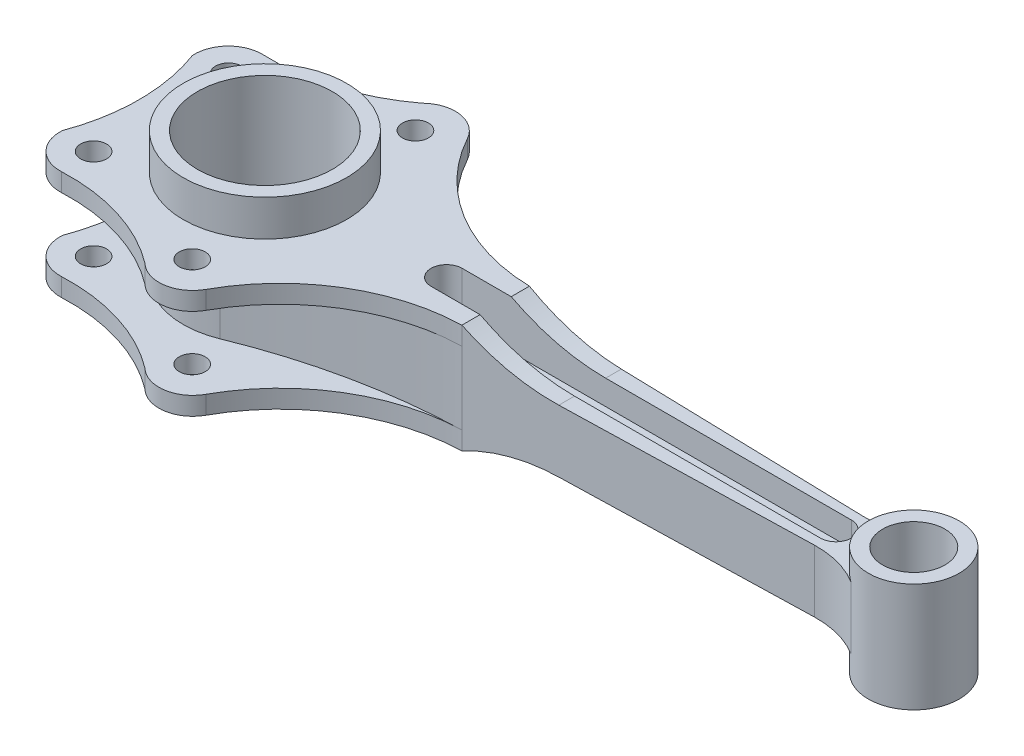
SolidWorks part; units mm, degrees
ref_plane "Front Plane" through (0, 0, 0) normal (0, 0, 1) x (1, 0, 0)
ref_plane "Top Plane" through (0, 0, 0) normal (0, 1, 0) x (1, 0, 0)
ref_plane "Right Plane" through (0, 0, 0) normal (1, 0, 0) x (0, 0, -1)
sketch "Sketch1" plane through (0, 0, 0) normal (0, 1, 0) x (1, 0, 0)
  line L0 (0, 96.3431) -> (0, -94.8456) construction
  line L1 (-187.9024, 0) -> (250, 0) construction
  line L2 (88.9041, 13.0022) -> (221.1878, 9.4949)
  line L3 (88.9041, -13.0022) -> (221.1878, -9.4949)
  line L4 (70, 0) -> (220, 0) construction
  line L5 (70, 6) -> (220, 6)
  line L6 (70, -6) -> (220, -6)
  circle A0 centre (0, 0) radius 31.5
  circle A1 centre (0, 0) radius 26
  circle A2 centre (250, 0) radius 17.5
  circle A3 centre (250, 0) radius 12
  circle A4 centre (15, 43) radius 5
  circle A5 centre (-40, 26) radius 5
  arc A6 (7.1798, 53.3914) -> (27.6805, 50.3597) centre (16.2817, 44.1094) cw
  arc A7 (-52.983, 25.0335) -> (-39.4311, 38.9301) centre (-40.0149, 25.9432) cw
  arc A8 (-39.4311, 38.9301) -> (7.1798, 53.3914) centre (-36.1982, 110.8575) ccw
  arc A9 (27.6805, 50.3597) -> (88.9041, 13.0022) centre (90.8125, 84.977) ccw
  circle A10 centre (-40, -26) radius 5
  circle A11 centre (15, -43) radius 5
  arc A12 (27.6805, -50.3597) -> (88.9041, -13.0022) centre (90.8125, -84.977) cw
  arc A13 (7.1798, -53.3914) -> (27.6805, -50.3597) centre (16.2817, -44.1094) ccw
  arc A14 (-52.983, -25.0335) -> (-39.4311, -38.9301) centre (-40.0149, -25.9432) ccw
  arc A15 (-39.4311, -38.9301) -> (7.1798, -53.3914) centre (-36.1982, -110.8575) cw
  arc A16 (-52.983, 25.0335) -> (-52.983, -25.0335) centre (-120.491, 0) cw
  arc A17 (240.7051, 14.8275) -> (221.1878, 9.4949) centre (222.1154, 44.4826) cw
  arc A18 (240.7051, -14.8275) -> (221.1878, -9.4949) centre (222.1154, -44.4826) ccw
  arc A19 (70, 6) -> (70, -6) centre (70, 0) ccw
  arc A20 (220, -6) -> (220, 6) centre (220, 0) ccw
  point P43 (145, 0)
  dimension "D1" = 63
  dimension "D2" = 52
  dimension "D4" = 24
  dimension "D5" = 35
  dimension "D6" = 10
  dimension "D7" = 10
  dimension "D12" = 13
  dimension "D13" = 13
  dimension "D14" = 72
  dimension "D15" = 72
  dimension "D16" = 72
  dimension "D17" = 35
  dimension "D18" = 35
  dimension "D19" = 6
  dimension "D3" = 250
  dimension "D8" = 15
  dimension "D9" = 26
  dimension "D10" = 17
  dimension "D11" = 40
  dimension "D20" = 150
  dimension "D21" = 30
  dimension "D23" = 3.4949
extrude "Boss-Extrude1" add sketch "Sketch1" along normal mid plane 42 contours A18 A2 A17 L2 A9 A6 A8 A7 A13 A12 L3 A20 L6 A19 L5 A10 A5 A4 A0 A11 | L6 A20 L5 A19 region at (41.4087, 0, 0)
sketch "Sketch2" plane through (0, 0, 0) normal (0, 0, 1) x (1, 0, 0)
  line L0 (240.7051, 21) -> (221.1878, 21) construction
  line L1 (88.9041, 21) -> (221.1878, 21) construction
  line L3 (240.7051, 21) -> (221.1878, 21)
  line L4 (88.9041, 21) -> (221.1878, 21)
  line L6 (0, 0) -> (269.5596, 0) construction
  line L7 (240.7051, 12) -> (125.2772, 12)
  line L9 (240.7051, 21) -> (240.7051, -21) construction
  line L10 (240.7051, -12) -> (125.2772, -12)
  line L11 (240.7051, -21) -> (221.1878, -21)
  line L12 (88.9041, -21) -> (221.1878, -21)
  line L13 (240.7051, 21) -> (240.7051, 12)
  line L14 (240.7051, -12) -> (240.7051, -21)
  arc A0 (88.9041, 21) -> (125.2772, 12) centre (125.2772, 90) ccw
  arc A1 (88.9041, -21) -> (125.2772, -12) centre (125.2772, -90) cw
  point P12 (0, 0)
  dimension "D2" = 78
  dimension "D1" = 9
extrude "Cut-Extrude1" cut sketch "Sketch2" against normal through all both and the other way through all
extrude "Boss-Extrude2" add sketch "Sketch1<3>" along normal mid plane 42 contours A2 A3 region at (258.2335, 0, -14.8788)
sketch "Sketch1<3>" plane through (0, 0, 0) normal (0, 1, 0) x (1, 0, 0) same geometry as "Sketch1"
extrude "Boss-Extrude3" add sketch "Sketch1<4>" along normal mid plane 70 contours A0 | A1
sketch "Sketch1<4>" plane through (0, 0, 0) normal (0, 1, 0) x (1, 0, 0) same geometry as "Sketch1"
extrude "Cut-Extrude2" cut sketch "Sketch1<5>" along normal blind 70 from offset 2.5 contours L6 A20 L5 A19 region at (145, 0, 0)
sketch "Sketch1<5>" plane through (0, 0, 0) normal (0, 1, 0) x (1, 0, 0) same geometry as "Sketch1"
mirror "Mirror1" about plane through (0, 0, 0) normal (0, 1, 0) of "Cut-Extrude2"
sketch "Sketch5" plane through (0, 0, 0) normal (0, 1, 0) x (1, 0, 0)
  line L0 (0, 0) -> (88.9041, 0) construction
  line L1 (125.2772, 12.0379) -> (88.9041, 13.0022) construction
  arc A0 (88.9041, 13.0022) -> (11.8974, 29.1668) centre (94.7159, 232.1986) cw
  circle A1 centre (0, 0) radius 31.5 construction
  circle A2 centre (0, 0) radius 31.5 construction
  arc A3 (88.9041, -13.0022) -> (11.8974, -29.1668) centre (94.7159, -232.1986) ccw
  arc A4 (88.9041, -13.0022) -> (27.6805, -50.3597) centre (90.8125, -84.977) ccw
  arc A5 (88.9041, -13.0022) -> (27.6805, -50.3597) centre (90.8125, -84.977) ccw
  arc A6 (7.1798, -53.3914) -> (27.6805, -50.3597) centre (16.2817, -44.1094) ccw
  arc A7 (7.1798, -53.3914) -> (27.6805, -50.3597) centre (16.2817, -44.1094) ccw
  arc A8 (7.1798, -53.3914) -> (-39.4311, -38.9301) centre (-36.1982, -110.8575) ccw
  arc A9 (7.1798, -53.3914) -> (-39.4311, -38.9301) centre (-36.1982, -110.8575) ccw
  arc A10 (-52.983, -25.0335) -> (-39.4311, -38.9301) centre (-40.0149, -25.9432) ccw
  arc A11 (-52.983, -25.0335) -> (-39.4311, -38.9301) centre (-40.0149, -25.9432) ccw
  arc A12 (-52.983, -25.0335) -> (-52.983, 25.0335) centre (-120.491, 0) ccw
  arc A13 (-52.983, -25.0335) -> (-52.983, 25.0335) centre (-120.491, 0) ccw
  arc A14 (-39.4311, 38.9301) -> (-52.983, 25.0335) centre (-40.0149, 25.9432) ccw
  arc A15 (-39.4311, 38.9301) -> (-52.983, 25.0335) centre (-40.0149, 25.9432) ccw
  arc A16 (-39.4311, 38.9301) -> (7.1798, 53.3914) centre (-36.1982, 110.8575) ccw
  arc A17 (-39.4311, 38.9301) -> (7.1798, 53.3914) centre (-36.1982, 110.8575) ccw
  arc A18 (27.6805, 50.3597) -> (88.9041, 13.0022) centre (90.8125, 84.977) ccw
  arc A19 (27.6805, 50.3597) -> (88.9041, 13.0022) centre (90.8125, 84.977) ccw
  arc A20 (27.6805, 50.3597) -> (7.1798, 53.3914) centre (16.2817, 44.1094) ccw
  arc A21 (27.6805, 50.3597) -> (7.1798, 53.3914) centre (16.2817, 44.1094) ccw
  arc A22 (11.8974, 29.1668) -> (11.8974, -29.1668) centre (0, 0) ccw
  point P3 (0, 0)
extrude "Cut-Extrude3" cut sketch "Sketch5" against normal mid plane 28
